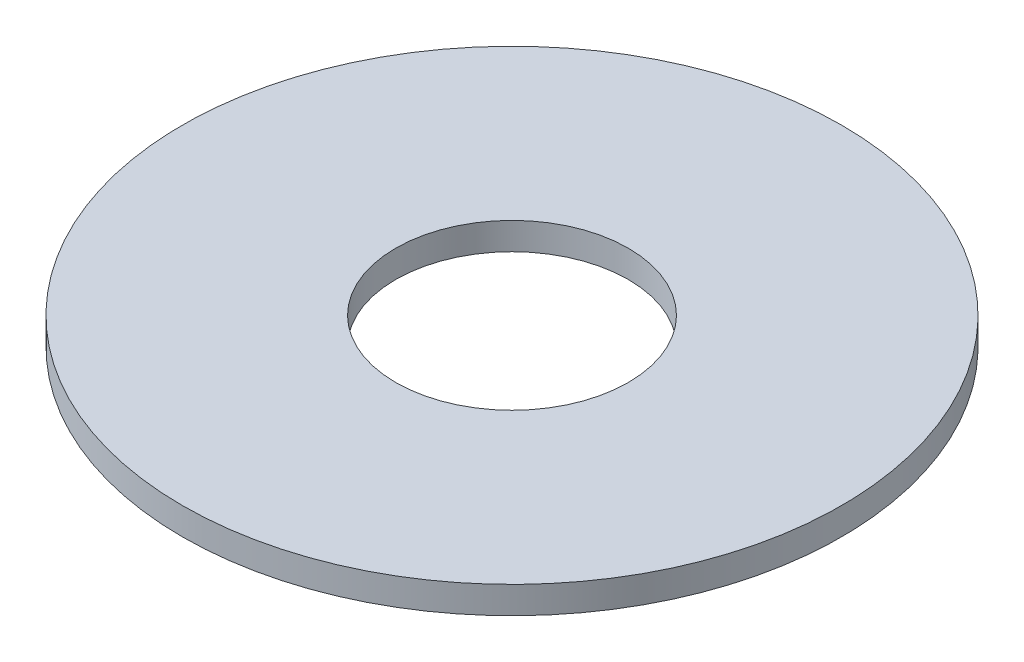
SolidWorks part; units mm, degrees
ref_plane "Front Plane" through (0, 0, 0) normal (0, 0, 1) x (1, 0, 0)
ref_plane "Top Plane" through (0, 0, 0) normal (0, 1, 0) x (1, 0, 0)
ref_plane "Right Plane" through (0, 0, 0) normal (1, 0, 0) x (0, 0, -1)
sketch "Sketch1" plane through (0, 0, 0) normal (0, 1, 0) x (1, 0, 0)
  circle A0 centre (0, 0) radius 85
  dimension "FLANGE_OD" = 170
extrude "Boss-Extrude1" add sketch "Sketch1" along normal blind 7
sketch "Sketch2" plane through (0, 0, 0) normal (0, 1, 0) x (1, 0, 0)
  circle A0 centre (0, 0) radius 30
  dimension "BORE_D" = 60
extrude "Cut-Extrude1" cut sketch "Sketch2" along normal through all
sketch "Sketch3" plane through (0, 7, 0) normal (0, 1, 0) x (1, 0, 0)
  circle A0 centre (0, 0) radius 23.6044 construction
  circle A1 centre (-23.6044, 0) radius 4.1222
  dimension "BOLT_D" = 8.2445
  dimension "BOLT_PCD" = 47.2089
extrude "Cut-Extrude2" cut sketch "Sketch3" against normal blind 5.9899 rebuild error yes
pattern_circular "CirPattern1" count 6 over 360 rebuild error yes
